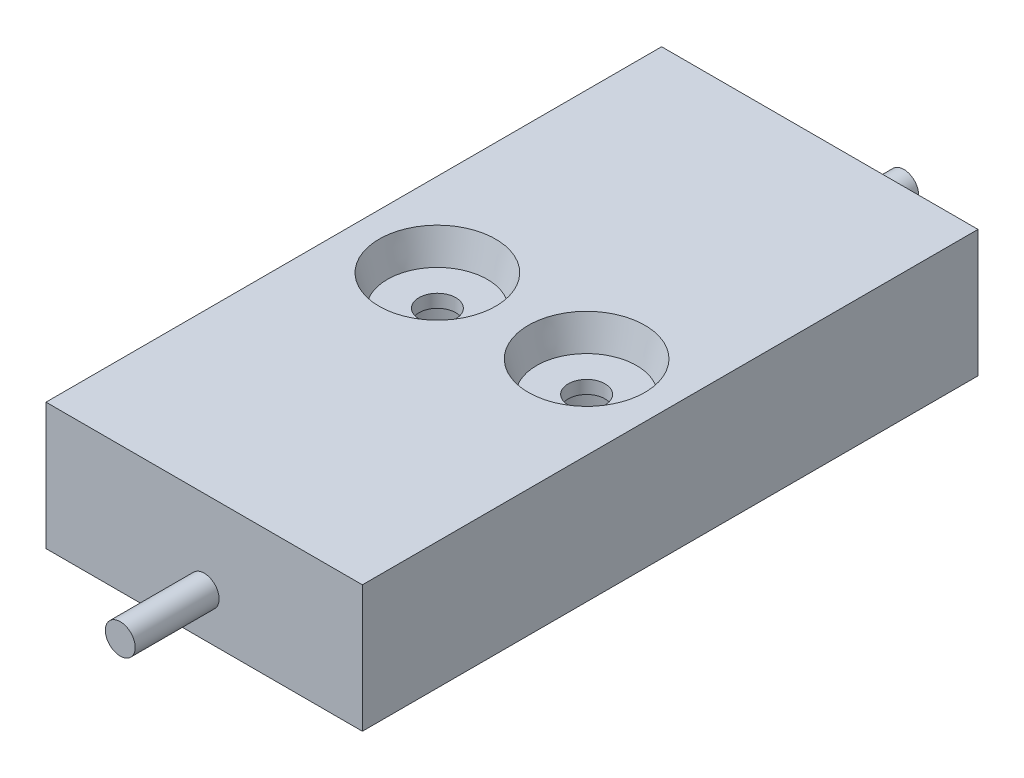
SolidWorks part; units mm, degrees
material "ABS"
ref_plane "Front Plane" through (0, 0, 0) normal (0, 0, 1) x (1, 0, 0)
ref_plane "Top Plane" through (0, 0, 0) normal (0, 1, 0) x (1, 0, 0)
ref_plane "Right Plane" through (0, 0, 0) normal (1, 0, 0) x (0, 0, -1)
sketch "Sketch1" plane through (0, 0, 0) normal (0, 1, 0) x (1, 0, 0)
  line L0 (-20, 0) -> (20, 0) construction
  line L1 (0, -82.5) -> (0, 82.5) construction
  line L3 (-42.4, 82.5) -> (42.4, 82.5)
  line L4 (-42.4, 82.5) -> (-42.4, -82.5)
  line L5 (-42.4, -82.5) -> (42.4, -82.5)
  line L6 (42.4, 82.5) -> (42.4, -82.5)
  circle A0 centre (-20, 0) radius 4.925
  circle A1 centre (20, 0) radius 4.925
  circle A2 centre (-20, 0) radius 13.4
  circle A3 centre (20, 0) radius 13.4
  dimension "D1" = 9.85
  dimension "D3" = 26.8
  dimension "D4" = 9
  dimension "D2" = 40
  dimension "D5" = 165
extrude "Boss-Extrude1" add sketch "Sketch1" along normal mid plane 3.5 contours L6 L3 L4 L5 A2 A3 | A2 A0 | A3 A1 region at (0, 0, 0) region at (-33.021, 0, 0) region at (6.979, 0, 0)
extrude "Boss-Extrude2" add sketch "Sketch1<3>" along normal blind 10 contours L6 L3 L4 L5 A2 A3 region at (0, 0, 0)
sketch "Sketch1<3>" plane through (0, 0, 0) normal (0, 1, 0) x (1, 0, 0) same geometry as "Sketch1"
extrude "Boss-Extrude3" add sketch "Sketch1<4>" against normal blind 24 contours L6 L3 L4 L5 A2 A3 region at (0, 0, 0)
sketch "Sketch1<4>" plane through (0, 0, 0) normal (0, 1, 0) x (1, 0, 0) same geometry as "Sketch1"
sketch "Sketch4" plane through (0, 0, 0) normal (0, 0, 1) x (1, 0, 0)
  line L0 (0, 0) -> (0, 18.0942) construction
  line L2 (0, 0) -> (-8.5015, 12.1414) construction
  line L3 (-8.5015, 12.1414) -> (0, 18.0942) construction
  dimension "D1" = 35
draft "Draft1" type of draft neutral plane draft angle 15 faces to draft 2 face at (-20, 1.75, 13.4) face at (20, 1.75, 13.4) neutral plane through (0, 1.75, 0) neutral plane normal (0, 1, 0) parameters "D1"=15
sketch "Sketch5" plane through (0, 0, 0) normal (0, 0, 1) x (1, 0, 0)
  circle A0 centre (0, -12.5) radius 4
  point P2 (0, 0)
  dimension "D1" = 8
  dimension "D2" = 12.5
extrude "Cut-Extrude1" cut sketch "Sketch5" against normal through all both and the other way through all
extrude "Boss-Extrude4" add sketch "Sketch5<2>" along normal mid plane 210 separate body
sketch "Sketch5<2>" plane through (0, 0, 0) normal (0, 0, 1) x (1, 0, 0) same geometry as "Sketch5"
